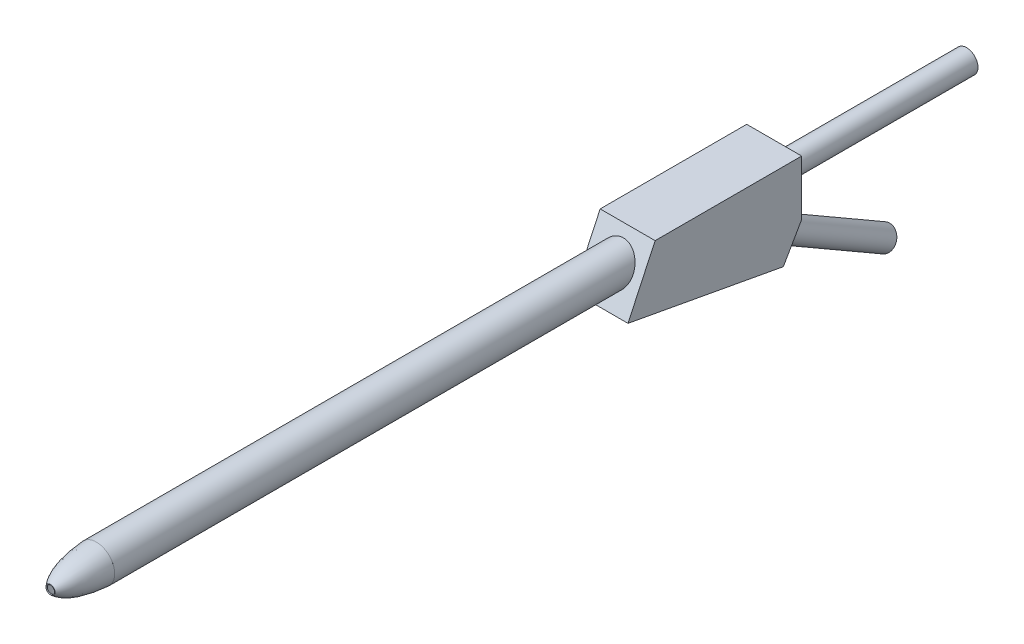
SolidWorks part; units mm, degrees
ref_plane "Front" through (0, 0, 0) normal (0, 0, 1) x (1, 0, 0)
ref_plane "Top" through (0, 0, 0) normal (0, 1, 0) x (1, 0, 0)
ref_plane "Right" through (0, 0, 0) normal (1, 0, 0) x (0, 0, -1)
sketch "Sketch2" plane through (0, 0, 0) normal (1, 0, 0) x (0, 0, -1)
  line L0 (0, 0) -> (16, 0)
  line L1 (0, 0) -> (-2.9616, -6.3426)
  line L2 (16, 0) -> (16, -6)
  line L3 (16, -6) -> (14, -9.4641)
  line L4 (16, 0) -> (16, -15.7704) construction
  line L5 (14, -9.4641) -> (-2.9616, -6.3426)
  dimension "D1" = 16
  dimension "D2" = 6
  dimension "D3" = 30
  dimension "D4" = 4
  dimension "D5" = 7
extrude "Boss-Extrude1" add sketch "Sketch2" along normal blind 6
sketch "Sketch3" plane through (0, 0, 0) normal (0, 0, 1) x (1, 0, 0)
  circle A0 centre (3, -3) radius 2
  circle A1 centre (3, -3) radius 1.25
  circle A2 centre (3, -3) radius 1.9
  circle A3 centre (3, -3) radius 1.15
  dimension "D1" = 4
  dimension "D2" = 2.5
  dimension "D3" = 0.1
  dimension "D4" = 0.1
extrude "Boss-Extrude2" add sketch "Sketch3" along normal blind 58 contours A0 A2 region at (1.0566, -3, 0)
extrude "Boss-Extrude3" add sketch "Sketch3<3>" against normal blind 37 contours A1 A3 region at (1.7854, -3, 0)
sketch "Sketch3<3>" plane through (0, 0, 0) normal (0, 0, 1) x (1, 0, 0) same geometry as "Sketch3"
ref_plane "Plane1" through (0, -8.4282, -14.5981) normal (0, -0.5, -0.866) x (-1, 0, 0)
sketch "Sketch4" plane through (0, -8.4282, -14.5981) normal (0, -0.5, -0.866) x (-1, 0, 0)
  circle A0 centre (-3, 0.8038) radius 1.25
  circle A2 centre (-3, 0.8038) radius 1.15
  dimension "D1" = 2.5
  dimension "D2" = 0.1
extrude "Boss-Extrude4" add sketch "Sketch4" along normal blind 15
ref_plane "Plane2" through (0, 0, 58) normal (0, 0, 1) x (1, 0, 0)
ref_plane "Plane3" through (0, 0, 63) normal (0, 0, 1) x (1, 0, 0)
ref_plane "Plane4" through (3, 0, 0) normal (1, 0, 0) x (0, 0, -1)
sketch "Sketch5" plane through (0, 0, 58) normal (0, 0, 1) x (1, 0, 0)
  circle A0 centre (3, -3) radius 2
sketch "Sketch6" plane through (0, 0, 63) normal (0, 0, 1) x (1, 0, 0)
  circle A0 centre (3, -3) radius 0.5
  dimension "D1" = 1
sketch "Sketch8" plane through (3, 0, 0) normal (1, 0, 0) x (0, 0, -1)
  line L1 (-58, 2.2) -> (-58, -2.2) construction
  line L2 (-0.4669, -1) -> (-58, -1) construction
  line L3 (-63, 2.2) -> (-63, -2.2) construction
  line L4 (-63, -2.5) -> (-63, -3.5) construction
  line L5 (-58, -1) -> (-57.9941, -1.0998)
  line L6 (-58, -3) -> (-65.6245, -3) construction
  line L7 (-58, -1) -> (-58, -5) construction
  arc A0 (-63, -2.5) -> (-62.9327, -2.574) centre (-62.9642, -2.535) ccw
  spline S0 degree 2 poles (-58, -1) (-61.5823, -1.2106) (-63, -2.5) knots 0 0 0 1 1 1
  spline S1 degree 1 poles (-57.9941, -1.0998) (-62.9327, -2.574) knots 0 0 1 1 construction
  spline S2 degree 3 poles (-57.9941, -1.0998) (-58.2803, -1.1167) (-58.8677, -1.1637) (-59.9117, -1.2999) (-61.0596, -1.5546) (-61.9715, -1.9166) (-62.5685, -2.2735) (-62.8143, -2.4663) (-62.9327, -2.574) knots 0 0 0 0 0.125 0.25 0.5 0.75 0.875 1 1 1 1
  dimension "D1" = 0.1
revolve "Revolve1" add sketch "Sketch8" angle 360 about L6
